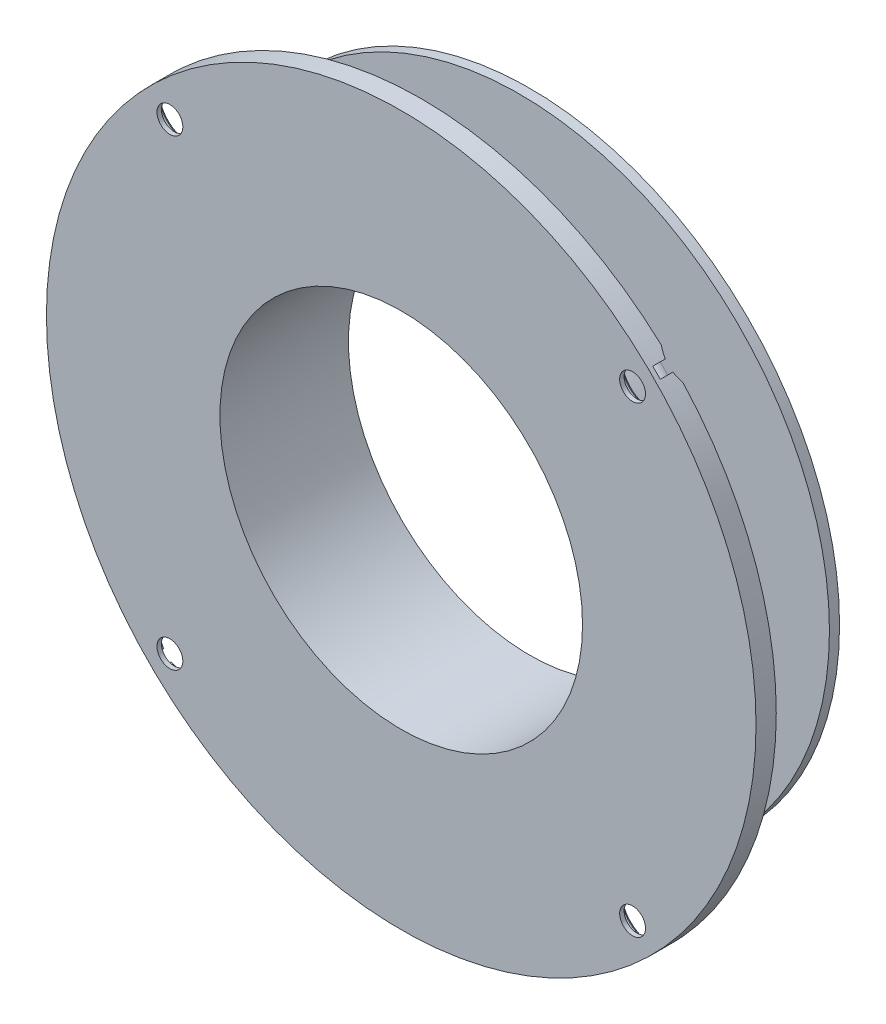
SolidWorks part; units mm, degrees
ref_plane "Front Plane" through (0, 0, 0) normal (0, 0, 1) x (1, 0, 0)
ref_plane "Top Plane" through (0, 0, 0) normal (0, 1, 0) x (1, 0, 0)
ref_plane "Right Plane" through (0, 0, 0) normal (1, 0, 0) x (0, 0, -1)
sketch "Sketch1" plane through (0, 0, 0) normal (0, 1, 0) x (1, 0, 0)
  line L2 (-1, -24.96) -> (-1, -10.64)
  line L3 (-1, -6.1) -> (1, -6.1)
  line L4 (1, -31.5) -> (1, -6.1)
  line L5 (0, 0) -> (1, -6.1) construction
  line L6 (0, 0) -> (1, -31.5) construction
  line L7 (-1, -6.1) -> (-24.4, -6.1)
  line L8 (-24.4, -6.1) -> (-24.4, -8.1)
  line L9 (-24.4, -8.1) -> (-3.54, -8.1)
  line L10 (1, -31.5) -> (-33.29, -31.5)
  line L11 (-33.29, -31.5) -> (-33.29, -27.5)
  line L12 (-33.29, -27.5) -> (-3.54, -27.5)
  arc A0 (-1, -24.96) -> (-3.54, -27.5) centre (-3.54, -24.96) cw
  arc A1 (-1, -10.64) -> (-3.54, -8.1) centre (-3.54, -10.64) ccw
  point P0 (0, 0)
  dimension "D6" = 2.54
  dimension "D7" = 34.29
  dimension "D1" = 2
  dimension "D2" = 19.4
  dimension "D3" = 23.4
  dimension "D4" = 2
  dimension "D5" = 4
  dimension "D8" = 2
ref_plane "Plane1" through (1, 0, 0) normal (1, 0, 0) x (0, 0, -1)
ref_plane "Plane2" through (36.83, 0, 0) normal (1, 0, 0) x (0, 0, -1)
ref_axis "Axis1" through (36.83, 0, 32.45) along (0, 0, -1)
revolve "Revolve1" add sketch "Sketch1" angle 360 about axis through (36.83, 0, 32.45) along (0, 0, -1)
sketch "Sketch5" plane through (0, 0, 27.5) normal (0, 0, -1) x (-1, 0, 0)
  line L6 (-82.55, -45.72) -> (8.89, -45.72)
  line L8 (-82.55, -45.72) -> (-82.55, 45.72)
  line L9 (-82.55, 45.72) -> (8.89, 45.72)
  line L10 (8.89, -45.72) -> (8.89, 45.72)
  line L11 (-82.55, -45.72) -> (8.89, 45.72) construction
  line L12 (-82.55, 45.72) -> (8.89, -45.72) construction
  circle A2 centre (-82.55, 45.72) radius 3.175
  circle A3 centre (8.89, 45.72) radius 3.175
  circle A4 centre (8.89, -45.72) radius 3.175
  circle A5 centre (-82.55, -45.72) radius 3.175
  point P0 (-36.83, 0)
  dimension "D1" = 91.44
  dimension "D3" = 6.35
  dimension "D4" = 6.35
  dimension "D5" = 6.35
  dimension "D6" = 6.35
  dimension "D2" = 91.44
hole_wizard "CBORE for #10 Binding Head Machine Screw1" positions "Sketch6" profile "Sketch7" counterbore size "#10" standard "ANSI Inch" end condition through all
sketch "Sketch6" plane through (0, 0, 27.5) normal (0, 0, -1) x (-1, 0, 0)
  point P0 (-82.55, 45.72)
  point P3 (8.89, 45.72)
  point P6 (8.89, -45.72)
  point P9 (-82.55, -45.72)
sketch "Sketch7" plane through (82.55, 45.72, 27.5) normal (1, 0, 0) x (0, 1, 0)
  line L0 (0, 0) -> (0, 4)
  line L1 (0, 4) -> (2.5527, 4)
  line L3 (2.5527, 4) -> (2.5527, 3.1242)
  line L4 (5.5562, 3.1242) -> (2.5527, 3.1242)
  line L5 (5.5562, 3.1242) -> (5.5562, 0.635)
  line L6 (5.5562, 0.635) -> (6.1913, 0)
  line L7 (6.1913, 0) -> (0, 0)
  line L8 (-5.5562, 0.635) -> (-6.1913, 0) construction
  line L11 (0, -6.35) -> (0, 107.95) construction
  dimension "Thru Hole Dia." = 5.1054
  dimension "Thru Hole Depth" = 4
  dimension "C'Bore Dia." = 11.1125
  dimension "C'Bore Depth" = 3.1242
  dimension "Near C'Sink Dia." = 12.3825
  dimension "Near C'Sink Angle" = 90
